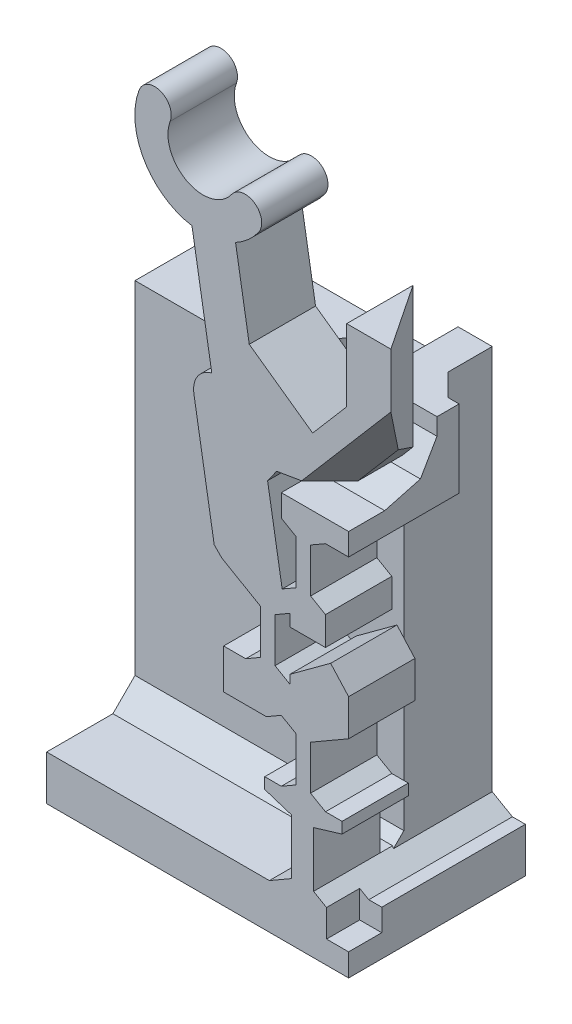
SolidWorks part; units mm, degrees
ref_plane "Front Plane" through (0, 0, 0) normal (0, 0, 1) x (1, 0, 0)
ref_plane "Top Plane" through (0, 0, 0) normal (0, 1, 0) x (1, 0, 0)
ref_plane "Right Plane" through (0, 0, 0) normal (1, 0, 0) x (0, 0, -1)
sketch "Sketch-SkeletonConfigUp" plane through (0, 0, 0) normal (0, 0, 1) x (1, 0, 0)
  line L0 (0, 0) -> (0, -50000) construction
  line L1 (0, 0) -> (4.5811, 6.2164) construction
  line L2 (9.8143, 13.3177) -> (4.5811, 13.945) construction
  line L3 (4.5811, 13.945) -> (2.9713, 10.4094) construction
  line L4 (2.9713, 10.4094) -> (4.5811, 6.2164) construction
  line L5 (4.5811, 13.945) -> (6.2429, 19.1409) construction
  line L6 (2.9713, 10.4094) -> (0.0405, 27.8193) construction
  line L7 (4.5811, 6.2164) -> (9.8143, 13.3177) construction
  line L8 (-587.3593, -797.0242) -> (9.8143, 13.3177) construction
  dimension "D2" = 7.7221
  dimension "D3" = 8.8212
  dimension "D4" = 5.2707
  dimension "D5" = 119.553
  dimension "D6" = 3.8848
  dimension "D7" = 5.4552
  dimension "D8" = 17.6549
  dimension "D9" = 4.4914
  dimension "D10" = 6.745
  dimension "D11" = 145.964
  dimension "D12" = 143.612
sketch "Sketch-SkeletonConfigDown" plane through (0, 0, 0) normal (0, 0, 1) x (1, 0, 0)
  line L0 (0, 0) -> (0, -50000) construction
  line L1 (0, 0) -> (4.5811, 6.2164) construction
  line L2 (9.8143, 13.3177) -> (4.5811, 13.945) construction
  line L3 (4.5811, 13.945) -> (6.1909, 10.4094) construction
  line L4 (6.1909, 10.4094) -> (4.5811, 6.2164) construction
  line L5 (4.5811, 13.945) -> (1.753, 18.6098) construction
  line L6 (6.1909, 10.4094) -> (-8.8652, 19.6294) construction
  line L7 (4.5811, 6.2164) -> (9.8143, 13.3177) construction
  line L8 (-589.9357, -800.5203) -> (9.8143, 13.3177) construction
  dimension "D2" = 7.7221
  dimension "D3" = 8.8212
  dimension "D4" = 5.2707
  dimension "D5" = 119.553
  dimension "D6" = 3.8848
  dimension "D7" = 5.4552
  dimension "D8" = 17.6549
  dimension "D9" = 4.4914
  dimension "D10" = 6.745
  dimension "D11" = 145.964
  dimension "D1" = 143.612
ref_plane "Plane-Cam Base" through (9.128, 0, 0) normal (1, 0, 0) x (0, 0, -1)
ref_plane "Plane-Down-to-Up Derailleur Clearance" through (6.628, 0, 0) normal (1, 0, 0) x (0, 0, -1)
ref_plane "Plane-Cam Cavity Roof" through (5.128, 0, 0) normal (1, 0, 0) x (0, 0, -1)
sketch "Sketch-SwitchBossUp" plane through (0, 0, 0) normal (0, 0, 1) x (1, 0, 0)
  line L0 (3.5811, 11.4759) -> (3.5811, 12.945) construction
  line L2 (6.5405, 21.1774) -> (6.5405, 24.4384)
  line L3 (6.5405, 24.4384) -> (8.5405, 24.4384)
  line L4 (8.5405, 24.4384) -> (8.5405, 20.4384)
  line L5 (5.5811, 12.5552) -> (5.5811, 11.263)
  line L7 (1.5115, 25.1048) -> (2.5464, 18.9575)
  line L8 (-0.4607, 24.7728) -> (0.4359, 19.4465)
  line L9 (2.9713, 10.4094) -> (0.0405, 27.8193) construction
  line L11 (-0.0396, 22.2712) -> (1.9326, 22.6032) construction
  line L15 (6.628, -23.7286) -> (6.628, 23.7286) construction
  line L16 (2.9713, 10.4094) -> (4.5811, 6.2164) construction
  line L17 (3.5811, 12.945) -> (3.5811, 14.945) construction
  line L18 (5.5811, 12.945) -> (5.5811, 14.945) construction
  line L19 (4.2561, 13.945) -> (4.9061, 13.945) construction
  line L20 (3.5811, 14.945) -> (5.5811, 14.945) construction
  line L21 (3.5811, 12.945) -> (5.5811, 12.945) construction
  line L22 (4.5811, 12.945) -> (4.5811, 14.945) construction
  line L23 (4.5811, 6.2164) -> (8.5405, 7.1023) construction
  line L24 (1.9713, 9.4094) -> (1.9713, 11.4094) construction
  line L25 (3.9713, 9.4094) -> (3.9713, 11.4094) construction
  line L26 (3.9713, 9.4094) -> (1.9713, 9.4094) construction
  line L27 (1.9713, 11.4094) -> (3.9713, 11.4094) construction
  line L28 (3.5811, 7.2164) -> (5.5811, 7.2164) construction
  line L29 (3.5811, 7.2164) -> (3.5811, 5.2164) construction
  line L30 (5.5811, 7.2164) -> (5.5811, 5.2164) construction
  line L31 (3.5811, 5.2164) -> (5.5811, 5.2164) construction
  line L32 (4.9061, 6.2164) -> (4.2561, 6.2164) construction
  line L40 (3.2963, 10.4094) -> (2.6463, 10.4094) construction
  line L43 (2.874, 4.5093) -> (0.7934, 4.5093) construction
  line L46 (5.0405, 1.437) -> (5.0405, 3.937)
  line L51 (4.9929, 19.3693) -> (2.5464, 18.9575)
  line L66 (0.0405, 27.8193) -> (0.0405, 50027.8193) construction
  line L74 (0.5455, 12.7717) -> (-0.3728, 18.2264)
  line L75 (0.3841, 13.7302) -> (2.3564, 14.0622) construction
  line L76 (5.5811, 11.263) -> (5.5811, 12.5552) construction
  line L77 (5.5811, 7.6061) -> (6.628, 8.2105)
  line L80 (5.8152, 10.763) -> (6.628, 9.8603)
  line L81 (8.5405, 1033.6218) -> (8.5405, 20.4384) construction
  line L82 (2.5464, 18.9575) -> (3.5585, 12.945) construction
  line L83 (3.6203, 12.5779) -> (2.8784, 16.9852)
  line L84 (2.8784, 16.9852) -> (6.0405, 17.5175)
  line L85 (6.9307, 9.5241) -> (8.5405, 7.7363) construction
  line L88 (3.5811, 16.3347) -> (6.8573, 16.3347)
  line L92 (3.7762, 8.3129) -> (6.9307, 9.5241) construction
  line L93 (6.3311, 4.3267) -> (5.0405, 3.937)
  line L95 (2.5464, 18.9575) -> (2.8784, 16.9852) construction
  line L96 (2.7124, 17.9713) -> (8.5405, 18.9524) construction
  line L97 (2.7124, 17.9713) -> (1.7262, 17.8053) construction
  line L98 (1.9713, 9.0197) -> (0.9713, 9.0197)
  line L99 (0.9713, 9.0197) -> (0.9713, 7.2164)
  line L100 (0.9713, 7.2164) -> (2.9061, 7.2164)
  line L101 (4.5811, 6.2164) -> (6.9307, 9.5241) construction
  line L103 (0.0405, 27.8193) -> (1.9448, 26.4638) construction
  line L104 (6.9307, 9.5241) -> (8.5405, 7.7363) construction
  line L106 (13.4416, 14.945) -> (5.5811, 14.945) construction
  line L107 (1.9713, 9.4094) -> (1.9713, 9.0197) construction
  line L109 (0.0405, 27.8193) -> (-2.1498, 28.6358) construction
  line L110 (8.5405, 20.4384) -> (6.0405, 17.5175)
  line L111 (6.628, 9.8603) -> (6.628, 8.2105)
  line L112 (6.628, 9.8603) -> (6.9307, 9.5241) construction
  line L113 (2.8311, 4.8267) -> (2.8311, 4.3267)
  line L114 (7.3693, 7.7363) -> (7.3563, 7.7363) construction
  line L115 (6.8573, 16.3347) -> (13.4416, 16.3347)
  line L116 (13.4416, 16.3347) -> (13.4416, -1.1653)
  line L117 (13.4416, -1.1653) -> (5.0405, -1.1653)
  line L119 (10.4375, 14.0252) -> (10.4375, 2.1692)
  line L121 (5.0405, -1.1653) -> (5.0405, 1.437) construction
  line L122 (8.237, 12.8031) -> (10.8393, 12.8031) construction
  line L123 (10.8393, 12.8031) -> (13.4416, 12.8031) construction
  line L124 (10.4375, 2.1692) -> (9.128, 0.8597)
  line L125 (8.5405, 7.5847) -> (13.4416, 7.5847) construction
  line L127 (5.5811, 15.3347) -> (5.5811, 14.945) construction
  line L130 (6.0405, 0.8597) -> (9.128, 0.8597)
  line L132 (2.8311, 4.3267) -> (4.0405, 3.937)
  line L133 (2.9713, 10.4094) -> (6.1909, 10.4094) construction
  line L134 (4.5811, 10.4094) -> (4.5811, 13.945) construction
  line L135 (4.5811, 10.4094) -> (4.5811, 6.2164) construction
  line L136 (0.8973, 12.4192) -> (0.5455, 12.7717)
  line L137 (3.9713, 9.4094) -> (5.5811, 7.2164) construction
  line L139 (5.8152, 10.763) -> (3.9713, 9.4094)
  line L140 (4.0405, 3.937) -> (4.0405, 1.437)
  line L141 (4.0405, 1.437) -> (3.0405, 0.8597)
  line L142 (3.0405, 0.8597) -> (3.0405, -1.1653)
  line L143 (8.5405, 20.4384) -> (8.5405, 18.9524) construction
  line L145 (8.5405, 17.9384) -> (8.5405, -49992.0368) construction
  line L147 (5.5811, 11.263) -> (5.5811, 12.5552) construction
  line L149 (6.3311, 4.8267) -> (6.3311, 4.3267)
  line L150 (3.0405, -1.1653) -> (5.0405, -1.1653)
  line L151 (4.0405, 3.937) -> (5.0405, 3.937) construction
  line L152 (4.2561, 14.945) -> (4.2561, 12.945)
  line L153 (4.9061, 14.945) -> (4.9061, 12.945)
  line L155 (4.2561, 14.945) -> (3.5811, 15.3347)
  line L156 (4.9061, 14.945) -> (5.5811, 15.3347)
  line L157 (3.5811, 16.3347) -> (3.5811, 15.3347)
  line L158 (5.5811, 15.3347) -> (9.128, 15.3347)
  line L162 (3.2963, 11.4094) -> (3.2963, 9.4094)
  line L164 (2.6463, 11.4094) -> (2.6463, 9.4094)
  line L169 (4.2561, 7.2164) -> (4.2561, 5.2164)
  line L170 (4.9061, 5.2164) -> (4.9061, 7.2164)
  line L175 (4.2561, 7.2164) -> (3.5811, 7.6061)
  line L176 (4.9061, 7.2164) -> (5.5811, 7.6061)
  line L177 (5.5811, 7.2164) -> (5.5811, 7.6061) construction
  line L179 (4.2561, 5.2164) -> (3.5811, 4.8267)
  line L180 (3.5811, 5.2164) -> (3.5811, 4.8267) construction
  line L181 (3.5811, 4.8267) -> (2.8311, 4.8267)
  line L183 (4.9061, 5.2164) -> (5.5811, 4.8267)
  line L184 (5.5811, 5.2164) -> (5.5811, 4.8267) construction
  line L186 (9.128, -23.7286) -> (9.128, 23.7286) construction
  line L187 (2.6463, 9.4094) -> (1.9713, 9.0197)
  line L188 (3.2963, 9.4094) -> (3.9713, 9.0197)
  line L189 (3.2963, 11.4094) -> (3.9713, 11.7991)
  line L190 (2.6463, 11.4094) -> (0.8973, 12.4192)
  line L191 (3.9713, 11.4094) -> (3.9713, 11.7991) construction
  line L192 (3.9713, 11.7991) -> (3.9713, 11.263)
  line L193 (4.9061, 12.945) -> (5.5811, 12.5552)
  line L194 (4.2561, 12.945) -> (3.6203, 12.5779)
  line L195 (3.9713, 11.263) -> (5.5811, 11.263)
  line L196 (3.9713, 9.4094) -> (3.9713, 9.0197)
  line L197 (3.5811, 7.2164) -> (3.5811, 7.6061) construction
  line L199 (3.5811, 7.6061) -> (2.9061, 7.2164)
  line L200 (5.5811, 4.8267) -> (6.3311, 4.8267)
  line L201 (2.8311, 4.3267) -> (2.8311, 3.937) construction
  line L202 (2.8311, 3.937) -> (4.0405, 3.937) construction
  line L203 (10.4375, 14.0252) -> (9.128, 15.3347)
  line L204 (4.0405, 1.437) -> (3.0405, 1.437) construction
  line L205 (3.0405, 1.437) -> (3.0405, 0.8597) construction
  line L206 (5.0405, 1.437) -> (6.0405, 0.8597)
  line L207 (8.5405, 18.9524) -> (8.5405, 17.9384) construction
  line L208 (6.0405, 17.5175) -> (8.5405, 17.9384) construction
  line L209 (8.5405, 20.4384) -> (8.5405, 17.9384) construction
  line L210 (6.5405, 21.1774) -> (4.9929, 19.3693)
  arc A0 (1.5115, 25.1048) -> (2.5558, 26.0289) centre (0.0405, 27.8193) ccw
  arc A1 (-0.4607, 24.7728) -> (-2.8525, 28.8978) centre (0.0405, 27.8193) cw
  arc A2 (-2.8525, 28.8978) -> (-1.447, 28.3738) centre (-2.1498, 28.6358) cw
  arc A3 (2.5558, 26.0289) -> (1.3338, 26.8987) centre (1.9448, 26.4638) ccw
  arc A4 (-1.447, 28.3738) -> (1.3338, 26.8987) centre (0.0405, 27.8193) ccw
  arc A5 (3.5811, 12.945) -> (3.5811, 14.945) centre (3.1778, 13.945) ccw construction
  arc A6 (5.5811, 12.945) -> (5.5811, 14.945) centre (5.9843, 13.945) cw construction
  arc A7 (2.5293, 9.921) -> (1.9713, 11.4094) centre (1.568, 10.4094) ccw construction
  arc A8 (3.9713, 11.4094) -> (3.9713, 9.4094) centre (4.3745, 10.4094) ccw construction
  arc A9 (3.5811, 7.2164) -> (3.5811, 5.2164) centre (3.1779, 6.2164) cw construction
  arc A10 (5.5811, 7.2164) -> (5.5811, 5.2164) centre (5.9844, 6.2164) ccw construction
  arc A19 (-0.3728, 18.2264) -> (0.4359, 19.4465) centre (0.6836, 18.4042) cw
  circle A28 centre (0.0405, 27.8193) radius 2.3375 construction
  arc A29 (1.9713, 9.4094) -> (2.5293, 9.921) centre (1.568, 10.4094) ccw construction
  point P53 (4.5811, 13.945)
  point P63 (2.9713, 10.4094)
  point P93 (0.9465, 22.4372)
  dimension "D23" = 1.5875
  dimension "D24" = 0.75
  dimension "D2" = 2
  dimension "D5" = 2
  dimension "D6" = 0.65
  dimension "D8" = 42
  dimension "D7" = 2
  dimension "D10" = 5
  dimension "D11" = 8.5
  dimension "D14" = 7.5
  dimension "D4" = 3
  dimension "D16" = 42
  dimension "D12" = 1
  dimension "D13" = 2.5
  dimension "D25" = 120
  dimension "D26" = 120
  dimension "D27" = 120
  dimension "D28" = 120
  dimension "D29" = 120
  dimension "D30" = 120
  dimension "D31" = 120
  dimension "D32" = 120
  dimension "D33" = 120
  dimension "D34" = 120
  dimension "D35" = 120
  dimension "D36" = 120
  dimension "D17" = 0.5
  dimension "D20" = 3.5
  dimension "D21" = 1
  dimension "D18" = 45
  dimension "D9" = 17.5
  dimension "D22" = 1
  dimension "D19" = 120
  dimension "D37" = 120
  dimension "D15" = 45
  dimension "D38" = 2
  dimension "D39" = 0.5
  dimension "D40" = 60
  dimension "D41" = 1
  dimension "D42" = 45
  dimension "D43" = 120
  dimension "D44" = 2
  dimension "D45" = 2.5
  dimension "D46" = 2.5
  dimension "D47" = 4
  dimension "D48" = 2
extrude "Boss-Switch Main" add sketch "Sketch-SwitchBossUp" along normal blind 3
sketch "Sketch1" plane through (0, 0, 0) normal (0, 0, -1) x (-1, 0, 0)
  line L0 (-3.5811, 16.3347) -> (-3.5811, 15.3347) construction
  line L1 (-7.5811, -1.1653) -> (0.4122, -1.1653)
  line L2 (-7.5811, -1.1653) -> (-7.5811, 0.8597)
  line L4 (0.4122, -1.1653) -> (0.4122, 0.8597)
  line L5 (-3.5811, 18.8347) -> (-7.5811, 18.8347)
  line L10 (-7.5811, 18.8347) -> (-7.5811, 15.3347)
  line L11 (-4.0405, 1.437) -> (-5.0405, 1.437)
  line L12 (-7.5811, 15.3347) -> (-3.5811, 15.3347)
  line L13 (-4.0405, 1.437) -> (-3.0405, 0.8597)
  line L14 (-3.5811, 15.3347) -> (-3.5811, 18.8347)
  line L22 (-3.0405, -1.1653) -> (-13.4416, -1.1653) construction
  line L23 (-3.0405, 0.8597) -> (0.4122, 0.8597)
  line L24 (-5.0405, 1.437) -> (-6.0405, 0.8597)
  line L25 (-6.0405, 0.8597) -> (-7.5811, 0.8597)
  line L26 (-9.128, 15.3347) -> (-5.5811, 15.3347) construction
  dimension "D1" = 3.5
  dimension "D4" = 4
extrude "Boss-Flange Width" add sketch "Sketch1" along normal blind 5
ref_plane "Plane-Sta2Sit Groove" through (0.0405, 0, 0) normal (1, 0, 0) x (0, 0, -1)
ref_plane "Plane-Cam Outer Surface" through (-12.0395, 0, 0) normal (1, 0, 0) x (0, 0, -1)
ref_plane "Plane-FlangeTop" through (-7.0395, 0, 0) normal (1, 0, 0) x (0, 0, -1)
sketch "Sketch2" plane through (-7.0395, 0, 0) normal (1, 0, 0) x (0, 0, -1)
  line L0 (5, 15.3347) -> (0, 15.3347) construction
  line L1 (5, 17.3347) -> (1, 17.3347)
  line L2 (5, 17.3347) -> (5, 15.3347)
  line L3 (5, 15.3347) -> (1, 15.3347)
  line L4 (1, 17.3347) -> (1, 15.3347)
  line L10 (-3, -1.1653) -> (-3, 16.3347) construction
  line L11 (5, 0.8597) -> (-3, 0.8597)
  line L12 (5, 0.8597) -> (5, -1.1653)
  line L13 (5, -1.1653) -> (-3, -1.1653)
  line L14 (-3, 0.8597) -> (-3, -1.1653)
  line L15 (0, 10.4094) -> (0, 27.8193) construction
  line L17 (5, 0.8597) -> (5, -1.1653) construction
  line L18 (-3, 0.8597) -> (0, 0.8597) construction
  dimension "D1" = 1
  dimension "D2" = 2
extrude "Boss-Flange Height" add sketch "Sketch2" along normal up to surface (11.6675 mm away)
sketch "Sketch10" plane through (0, 15.3347, 0) normal (0, 1, 0) x (1, 0, 0)
  line L0 (9.128, -23.7286) -> (9.128, 23.7286) construction
  line L1 (7.5811, 5) -> (5.128, 5)
  line L2 (7.5811, 5) -> (7.5811, 2)
  line L3 (7.5811, 2) -> (5.128, 2)
  line L5 (4.628, 7) -> (4.628, 1) construction
  line L6 (3.5811, 1) -> (-7.0395, 1) construction
  line L8 (5.128, 5) -> (5.128, 2)
  dimension "D1" = 1
  dimension "D2" = 0.5
  dimension "D3" = 4.5
extrude "Cut-Up-To-Down Derailleur Clearance" cut sketch "Sketch10" along normal up to next
sketch "Sketch17" plane through (0, 15.3347, 0) normal (0, -1, 0) x (1, 0, 0)
  line L0 (5.128, -5) -> (-7.0395, -5)
  line L1 (5.128, -5) -> (3.5811, -5) construction
  line L2 (-7.0395, -5) -> (-7.0395, -1)
  line L3 (-7.0395, -1) -> (5.128, -1)
  line L4 (5.128, -1) -> (5.128, -5)
  line L5 (-7.0395, -1) -> (-7.0395, -5) construction
extrude "Boss-Flange Support" add sketch "Sketch17" along normal up to surface (14.475 mm away) up to face at (-1.9995, 0.8597, -1)
sketch "Sketch-HolePositions" plane through (0, -1.1653, 0) normal (0, -1, 0) x (1, 0, 0)
  line L0 (-7.0395, -3) -> (7.5811, -3) construction
  line L1 (7.5811, -5) -> (-7.0395, -5) construction
  line L2 (7.5811, -5) -> (7.5811, 0) construction
  line L4 (-7.0395, -22.2167) -> (-7.0395, 22.2167) construction
  line L5 (3.5811, -1) -> (3.5811, -5) construction
  point P6 (-4.0395, -3)
  point P7 (0.5811, -3)
  dimension "D1" = 3
  dimension "D2" = 3
  dimension "D3" = 2
sketch "Sketch6" plane through (0, -1.1653, 0) normal (0, -1, 0) x (-1, 0, 0)
  point P0 (4.0395, 3)
  point P3 (-0.5811, 3)
hole_wizard "Tap Drill for M2x0.4 Tap1" positions "Sketch6" profile "Sketch5" hole size "M2x0.4" standard "ANSI Metric" end condition through all
sketch "Sketch5" plane through (-4.0395, -1.1653, -3) normal (1, 0, 0) x (0, 0, -1)
  line L0 (0, 0) -> (0, 30.5511)
  line L1 (0, 30.5511) -> (0.8, 30.5511)
  line L2 (0.8, 30.5511) -> (0.8, 0)
  line L5 (0.8, 0) -> (0, 0)
  line L11 (0, -6.35) -> (0, 107.95) construction
  dimension "Thru Hole Dia." = 1.6
  dimension "Thru Hole Depth" = 30.5511
sketch "Sketch9" plane through (0, -1.1653, 0) normal (0, -1, 0) x (1, 0, 0)
  point P0 (-4.0395, -3)
  point P3 (0.5811, -3)
hole_wizard "M2 Clearance Hole2" positions "Sketch9" profile "Sketch8" hole size "M2" standard "ANSI Metric"
sketch "Sketch8" plane through (-4.0395, -1.1653, -3) normal (1, 0, 0) x (0, 0, -1)
  line L0 (0, 0) -> (0, 15.721)
  line L1 (0, 15.721) -> (1.2, 15)
  line L2 (1.2, 15) -> (1.2, 0)
  line L5 (1.2, 0) -> (0, 0)
  line L10 (0, 15.721) -> (-1.2, 15) construction
  line L11 (0, -6.35) -> (0, 107.95) construction
  dimension "Hole Dia." = 2.4
  dimension "Hole Depth" = 15
  dimension "Drill Angle" = 118
sketch "Sketch-Measurements for Derailleur Ramps" plane through (0, 0, 0) normal (0, 0, 1) x (1, 0, 0)
  line L0 (2.8784, 16.9852) -> (2.5464, 18.9575)
  line L1 (2.7124, 17.9713) -> (1.7262, 17.8053)
  line L2 (2.9713, 10.4094) -> (0.0405, 27.8193) construction
  line L3 (1.7262, 17.8053) -> (-1.8937, 15.3603)
  line L4 (6.1909, 10.4094) -> (-8.8652, 19.6294) construction
  line L5 (1.7262, 17.8053) -> (2.6012, 12.6077)
  line L6 (2.6012, 12.6077) -> (-1.8937, 15.3603)
  line L7 (-0.0837, 16.5828) -> (-0.0837, 17.8053)
  line L8 (-0.0837, 17.8053) -> (1.7262, 17.8053)
  line L9 (6.1909, 10.4094) -> (2.9713, 10.4094)
  line L10 (5.386, 8.3129) -> (3.7762, 8.3129)
  line L12 (6.1909, 10.4094) -> (4.5811, 6.2164) construction
  line L13 (4.5811, 8.3129) -> (4.5811, 8.7912)
  line L14 (4.5811, 6.2164) -> (5.386, 8.3129)
  line L15 (2.9713, 10.4094) -> (4.5811, 6.2164) construction
  line L16 (3.7762, 8.3129) -> (4.5811, 6.2164)
  line L17 (5.386, 8.3129) -> (5.386, 8.7912)
  dimension "D1" = 1.81
  dimension "D2" = 0.8049
sketch "Sketch12" plane through (0, 24.4384, 0) normal (0, 1, 0) x (1, 0, 0)
  line L0 (6.5405, 0) -> (8.5405, -3)
  line L1 (8.5405, -3) -> (8.5405, 0)
  line L2 (8.5405, 0) -> (6.5405, 0)
extrude "Cut-Up-to-Down Cantilever Slope" cut sketch "Sketch12" against normal up to next
ref_plane "Plane1" through (0, 7.1023, 0) normal (0, 1, 0) x (1, 0, 0)
sketch "Sketch-Derailleur Location" plane through (0, 7.1023, 0) normal (0, 1, 0) x (1, 0, 0)
  line L0 (8.5405, 0) -> (8.5405, -3)
  line L1 (4.0405, -3) -> (3.0405, -3) construction
  line L2 (-119237.4187, 0) -> (9.8143, 0) construction
  point P0 (8.5405, 0)
  point P1 (0, 0)
  point P8 (8.5405, -1.5)
ref_plane "Plane-Cantilever Cut" [suppressed] through (7.0848, 8.5204, -1.9058) normal (-0.6301, -0.7578, 0.1695) x (-0.7765, 0.6151, -0.1368)
sketch "Sketch14" [suppressed] plane through (7.0848, 8.5204, -1.9058) normal (-0.6301, -0.7578, 0.1695) x (-0.7765, 0.6151, -0.1368)
  line L0 (2.3023, -1.6911) -> (-0.3551, -1.6911)
  line L2 (2.3023, -4.3362) -> (2.3023, -1.6911)
  line L3 (-0.3551, -1.6911) -> (-0.3551, -4.4608)
  line L5 (-0.3551, -4.4608) -> (1.0087, -5.0843)
  line L6 (1.0087, -5.0843) -> (2.3023, -4.3362)
extrude "Cut-Down-to-Up Cantilever Slope" [suppressed] cut sketch "Sketch14" against normal up to next
sketch "Sketch16" plane through (0, 0, 0) normal (0, 0, -1) x (-1, 0, 0)
  line L0 (-7.5811, 18.8347) -> (-13.4416, 18.8347)
  line L1 (-13.4416, 18.8347) -> (-13.4416, -1.1653)
  line L2 (-13.4416, -1.1653) -> (-6.628, -1.1653)
  line L3 (-13.4416, -1.1653) -> (-5.0405, -1.1653) construction
  line L4 (-6.628, -1.1653) -> (-6.628, 5.2038)
  line L5 (-6.628, 5.2038) -> (-8.0037, 5.2038)
  line L6 (-8.0037, 5.2038) -> (-8.0037, 12.0484)
  line L7 (-8.0037, 12.0484) -> (-6.628, 12.0484)
  line L8 (-6.628, 12.0484) -> (-6.628, 17.9477)
  line L9 (-6.628, 23.7286) -> (-6.628, -23.7286) construction
  line L10 (-3.5811, 18.8347) -> (-6.5405, 18.8347) construction
  line L11 (-7.5811, 18.8347) -> (-6.628, 17.9477)
extrude "Cut-Down-to-Up Derailleur Clearance" cut sketch "Sketch16" against normal through all and the other way through all
ref_plane "Plane-Symmetry Plane" through (0, 0, 1.5) normal (0, 0, 1) x (1, 0, 0)
sketch "Sketch-Cable Center Point" plane through (0, 0, 1.5) normal (0, 0, 1) x (1, 0, 0)
  line L0 (0.0405, 27.8193) -> (0.1722, 27.0366)
  line L1 (2.9713, 10.4094) -> (0.0405, 27.8193) construction
  point P0 (0.0405, 27.8193)
  dimension "D1" = 0.7937
chamfer "Chamfer-Flange Support" distance 1.5 angle 45 1 edges at (3.5811, 17.3347, -3)
chamfer "Chamfer-Flange Support 2" distance 1 angle 45 2 edges at (5.128, 17.0847, -2) (5.128, 15.3347, -1.5)
chamfer "Chamfer-Flange Support 3" distance 1 angle 45 1 edges at (-1.9995, 0.8597, -1)
sketch "Sketch18" plane through (6.628, 0, 0) normal (1, 0, 0) x (0, 0, -1)
  line L1 (-3, -0.1403) -> (-1.5, -0.1403)
  line L2 (-3, -0.1403) -> (-3, 1.437)
  line L3 (-3, 1.437) -> (-1.5, 1.437)
  line L4 (-1.5, -0.1403) -> (-1.5, 1.437)
  line L5 (0.5774, 1.437) -> (0, 1.437) construction
  line L6 (-3, -1.1653) -> (-3, 0.8597) construction
  line L7 (-3, 0.8597) -> (5, 0.8597) construction
  dimension "D1" = 1.5
  dimension "D2" = 1
extrude "Cut-Down-to-Up Derailleur Clearance 2" cut sketch "Sketch18" against normal blind 1
sketch "Sketch19" plane through (0, 0, 0) normal (0, 0, 1) x (1, 0, 0)
  line L7 (3.5811, 18.8347) -> (6.628, 18.8347)
  line L8 (6.628, 18.8347) -> (6.628, 16.3347)
  line L9 (6.628, 16.3347) -> (3.5811, 16.3347)
  line L10 (3.5811, 16.3347) -> (3.5811, 18.8347)
  line L11 (6.628, 16.3347) -> (6.628, 17.9477) construction
extrude "Cut-Up-to-Down Cantilever Clearance" cut sketch "Sketch19" against normal up to surface (1 mm away) up to face at (1.4435, 12.7784, -1)
chamfer "Chamfer1" distance 1 angle 60 1 edges at (5.1045, 16.3347, -1) first distance on face at (5.1045, 16.3347, 1)
chamfer "Chamfer3" distance 0.75 angle 60 1 edges at (3.5811, 16.7007, -1) first distance on face at (3.5811, 16.1233, 0.6667)
chamfer "Chamfer4" distance 0.5 angle 60 1 edges at (4.205, 15.3347, -1) first distance on face at (5.1242, 15.3347, -0.0278)
chamfer "Chamfer5" distance 0.5 angle 45 1 edges at (2.8784, 16.9852, 1.5)
chamfer "Chamfer6" distance 2.5 angle 45 1 edges at (2.5464, 18.9575, 1.5)
chamfer "Chamfer7" distance 1 angle 45 1 edges at (7.2905, 18.978, 3)
sketch "Sketch22" plane through (0, 0, 0) normal (0, 0, 1) x (1, 0, 0)
  line L0 (6.628, 17.9477) -> (7.5811, 18.8347) construction
  line L1 (6.628, 18.8347) -> (7.5811, 18.8347) construction
  line L2 (6.628, 17.9477) -> (6.628, 18.8347) construction
  line L3 (6.628, 17.9477) -> (7.5811, 18.8347)
  line L4 (6.628, 18.8347) -> (7.5811, 18.8347)
  line L5 (6.628, 17.9477) -> (6.628, 18.8347)
extrude "Cut-Extrude3" cut sketch "Sketch22" against normal up to next
chamfer "Chamfer8" distance 0.5 angle 45 1 edges at (5.1045, 16.3347, 0) first distance on face at (4.2965, 17.2286, -0.5161)
equation "\"axle-diameter\"=2"
equation "\"switch-thickness\"=12"
equation "\"base-width\"=4.0"
equation "\"axle-bushing-radius\"=3"
equation "\"clearance\"= 0.25"
equation "\"arm-width\"=1.5"
equation "\"min-diameter\"=70"
equation "\"alpha\"=143.6120"
equation "\"gamma\"=119.5526"
equation "\"delta\"=145.9637"
equation "\"epsilon\"=6.7452"
equation "\"l_AB\"=8.8212"
equation "\"l_AC\"=4.4914"
equation "\"l_BD\"=5.2707"
equation "\"l_CD\"=3.8848"
equation "\"l_CE\"=17.6549"
equation "\"l_DF\"=5.4552"
equation "\"l_OA\"=7.7221"
equation "\"D2@Sketch-SkeletonConfigUp\" = \"l_OA\""
equation "\"D3@Sketch-SkeletonConfigUp\" = \"l_AB\""
equation "\"D4@Sketch-SkeletonConfigUp\" = \"l_BD\""
equation "\"D5@Sketch-SkeletonConfigUp\" = \"gamma\""
equation "\"D6@Sketch-SkeletonConfigUp\" = \"l_CD\""
equation "\"D7@Sketch-SkeletonConfigUp\" = \"l_DF\""
equation "\"D8@Sketch-SkeletonConfigUp\" = \"l_CE\""
equation "\"D9@Sketch-SkeletonConfigUp\" = \"l_AC\""
equation "\"D_groove\"=3.175"
equation "\"D7@Sketch-SkeletonConfigDown\" = \"l_DF\""
equation "\"D6@Sketch-SkeletonConfigDown\" = \"l_CD\""
equation "\"D2@Sketch-SkeletonConfigDown\" = \"l_OA\""
equation "\"D3@Sketch-SkeletonConfigDown\" = \"l_AB\""
equation "\"D9@Sketch-SkeletonConfigDown\" = \"l_AC\""
equation "\"D8@Sketch-SkeletonConfigDown\" = \"l_CE\""
equation "\"D5@Sketch-SkeletonConfigDown\" = \"gamma\""
equation "\"D4@Sketch-SkeletonConfigDown\" = \"l_BD\""
equation "\"D1@Sketch-SkeletonConfigDown\" = \"alpha\""
equation "\"hinge_length\"=1.5"
equation "\"hinge_depth\"=0.25"
equation "\"D10@Sketch-SkeletonConfigUp\"=\"epsilon\""
equation "\"D11@Sketch-SkeletonConfigUp\"=\"delta\""
equation "\"D12@Sketch-SkeletonConfigUp\"=\"alpha\""
equation "\"D11@Sketch-SkeletonConfigDown\"=\"delta\""
equation "\"D10@Sketch-SkeletonConfigDown\"=\"epsilon\""
equation "\"EE_dx\"=8.9056"
equation "\"EE_dy\"=8.1898"
equation "\"r_groove\"=\"D_groove\"/2"
equation "\"t_wall\"=25.4/16"
equation "\"width_lower\"=\"D_groove\"+\"t_wall\""
equation "\"cable_to_bottom\"=30.6257"
equation "\"switch_EE-up_base_dy\"=24"
equation "\"switch_EE-down_base_dy\"=16"
equation "\"D_axle\"=25.4/8"
equation "\"D_up_to_down\"=16"
equation "\"D_down_to_up\"=25"
equation "\"t_cam_base\"=7.5"
equation "\"D23@Sketch-SwitchBossUp\"=\"D_groove\"/2"
equation "\"D1@Sketch-Cable Center Point\"=\"D_groove\"/4"
